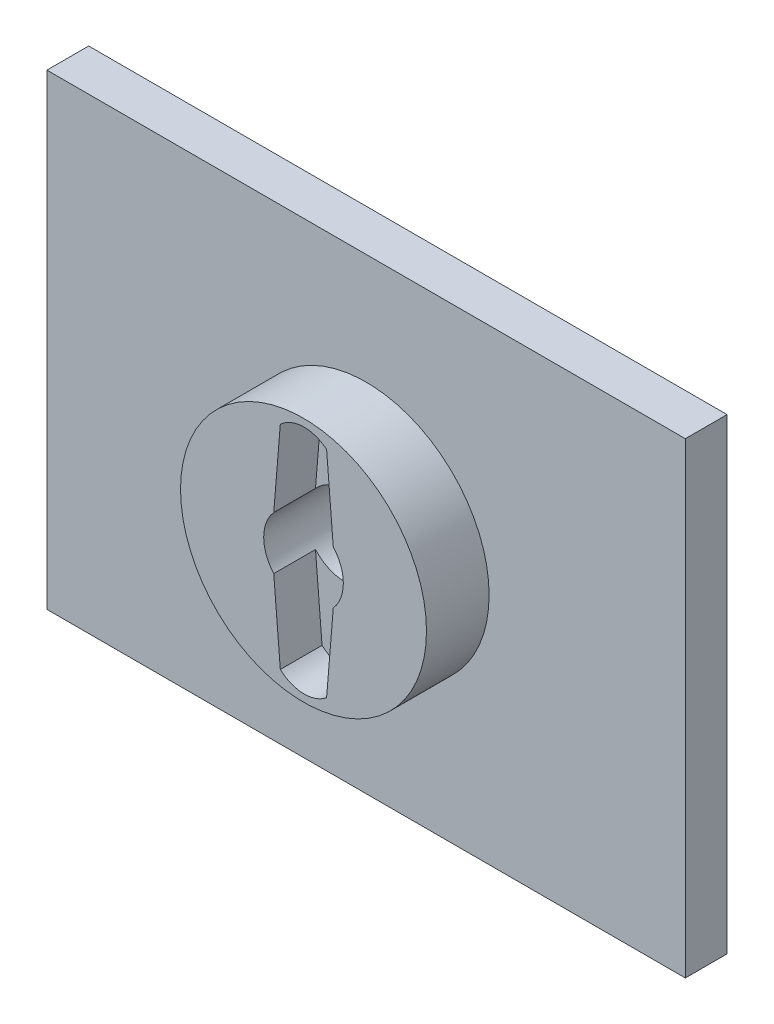
SolidWorks part; units mm, degrees
material "ABS"
ref_plane "Plan de face" through (0, 0, 0) normal (0, 0, 1) x (1, 0, 0)
ref_plane "Plan de dessus" through (0, 0, 0) normal (0, 1, 0) x (1, 0, 0)
ref_plane "Plan de droite" through (0, 0, 0) normal (1, 0, 0) x (0, 0, -1)
sketch "Esquisse1" plane through (0, 0, 0) normal (0, 0, 1) x (1, 0, 0)
  line L0 (30.5845, -22.376) -> (-30.5845, -22.376)
  line L1 (20.5845, 12.376) -> (-20.5845, 12.376) construction
  line L2 (20.5845, 12.376) -> (20.5845, -12.376) construction
  line L3 (20.5845, -12.376) -> (-20.5845, -12.376) construction
  line L4 (-20.5845, 12.376) -> (-20.5845, -12.376) construction
  line L5 (-30.5845, 22.376) -> (-30.5845, -22.376)
  line L6 (30.5845, 22.376) -> (-30.5845, 22.376)
  line L7 (30.5845, 22.376) -> (30.5845, -22.376)
  circle A0 centre (0, 0) radius 3.8155
extrude "Boss.-Extru.2" add sketch "Esquisse1" along normal blind 4 separate body
sketch "Esquisse2" plane through (0, 0, 0) normal (0, 0, 1) x (1, 0, 0)
  circle A0 centre (0, 0) radius 11.7835
extrude "Boss.-Extru.4" add sketch "Esquisse2" along normal blind 6 from offset 4
sketch "Esquisse4" plane through (0, 0, 10) normal (0, 0, 1) x (1, 0, 0)
  line L2 (2.8702, 2.3029) -> (2.2123, 10.3068)
  line L3 (-2.223, 10.1764) -> (-2.8702, 2.3029)
  line L4 (0, 0) -> (1.9304, 0) construction
  line L5 (-2.223, -10.1764) -> (-2.8702, -2.3029)
  line L6 (2.8702, -2.3029) -> (2.2123, -10.3068)
  arc A0 (-2.8702, 2.3029) -> (-2.8702, -2.3029) centre (0, 0) ccw
  arc A1 (-2.223, 10.1764) -> (2.2123, 10.3068) centre (0.0696, 7.6914) cw
  arc A2 (-2.223, -10.1764) -> (2.2123, -10.3068) centre (0.0696, -7.6914) ccw
  arc A3 (2.8702, -2.3029) -> (2.8702, 2.3029) centre (0, 0) ccw
extrude "Enlèv. mat.-Extru.1" cut sketch "Esquisse4" against normal blind 4
extrude "Enlèv. mat.-Extru.3" cut sketch "Esquisse1<2>" along normal through all contours A0 region at (0, 0, 0)
sketch "Esquisse1<2>" plane through (0, 0, 0) normal (0, 0, 1) x (1, 0, 0) same geometry as "Esquisse1"
